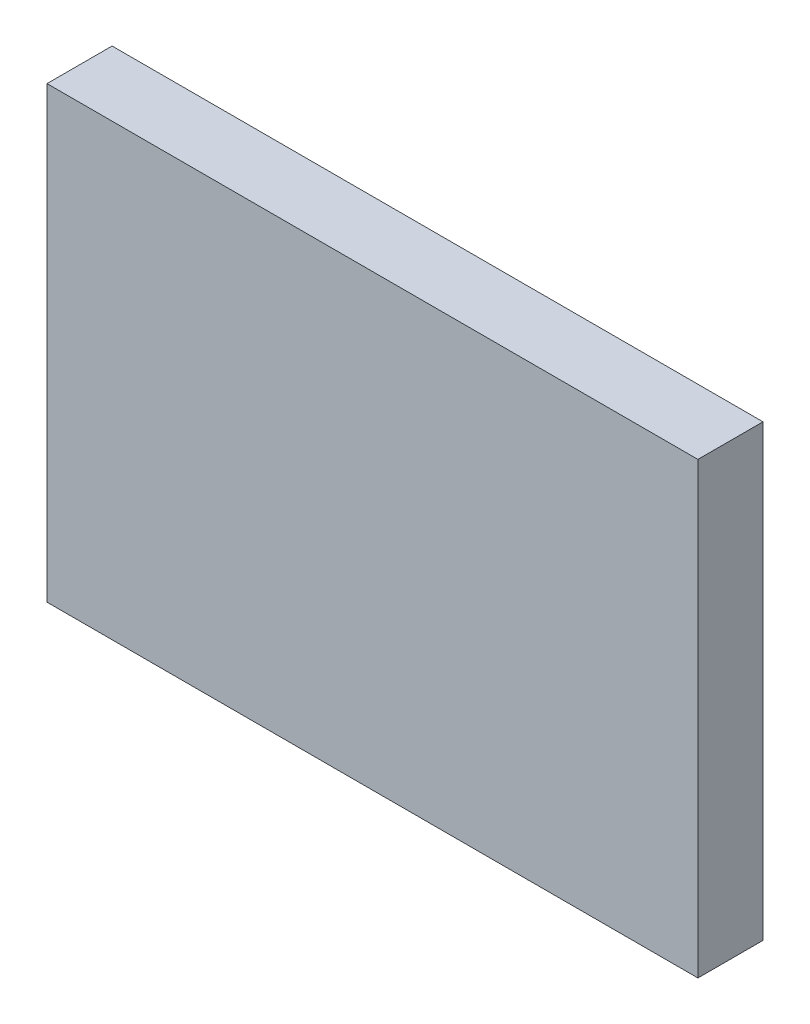
SolidWorks part; units mm, degrees
ref_plane "前视基准面" through (0, 0, 0) normal (0, 0, 1) x (1, 0, 0)
ref_plane "上视基准面" through (0, 0, 0) normal (0, 1, 0) x (1, 0, 0)
ref_plane "右视基准面" through (0, 0, 0) normal (1, 0, 0) x (0, 0, -1)
other "Configuration Table"
sketch "草图1" plane through (0, 0, 0) normal (0, 0, 1) x (1, 0, 0)
  line L1 (-50, -34.5) -> (50, -34.5)
  line L2 (-50, -34.5) -> (-50, 34.5)
  line L3 (-50, 34.5) -> (50, 34.5)
  line L4 (50, -34.5) -> (50, 34.5)
  line L5 (-50, -34.5) -> (50, 34.5) construction
  line L6 (-50, 34.5) -> (50, -34.5) construction
  point P0 (0, 0)
  dimension "D1" = 69
  dimension "D2" = 100
extrude "凸台-拉伸1" add sketch "草图1" along normal blind 10
